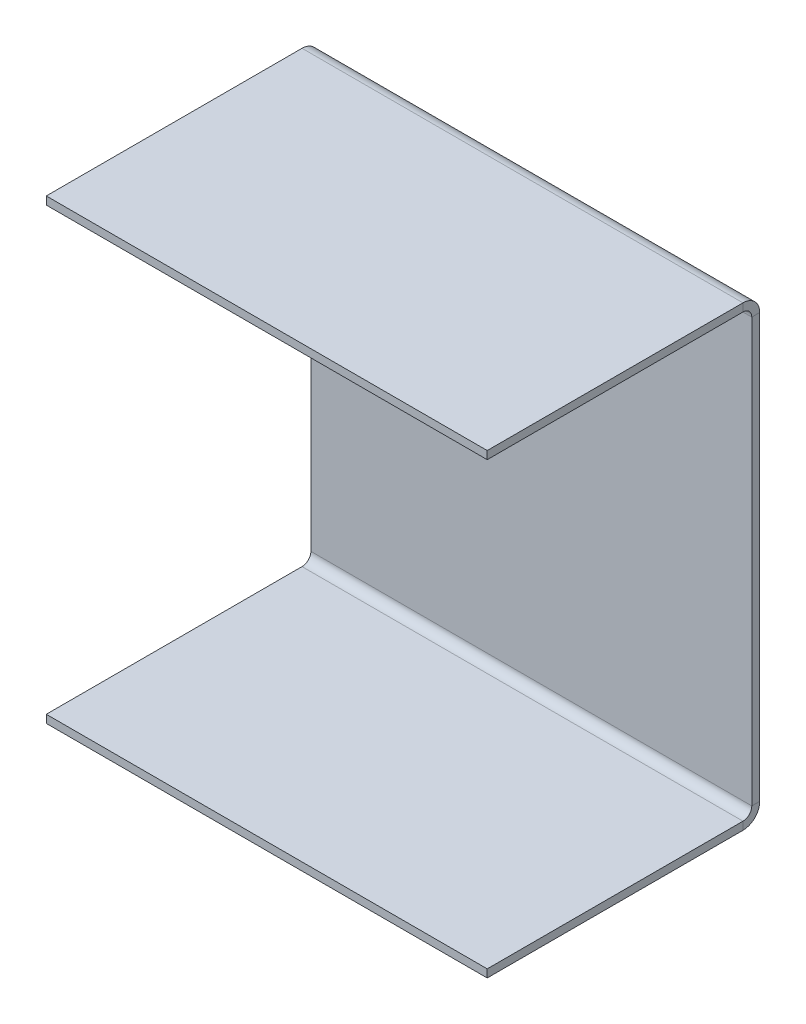
SolidWorks part; units mm, degrees
note: The reader was unsure of these and kept them because the rebuilt part matched: flange length of "Edge-Flange1", "Edge-Flange2".
ref_plane "Front Plane" through (0, 0, 0) normal (0, 0, 1) x (1, 0, 0)
ref_plane "Top Plane" through (0, 0, 0) normal (0, 1, 0) x (1, 0, 0)
ref_plane "Right Plane" through (0, 0, 0) normal (1, 0, 0) x (0, 0, -1)
sketch "Sketch1" plane through (0, 0, 0) normal (0, 0, 1) x (1, 0, 0)
  line L0 (25, 25) -> (-25, -25) construction
  line L1 (-25, 25) -> (25, 25)
  line L2 (-25, 25) -> (-25, -25)
  line L3 (-25, -25) -> (25, -25)
  line L4 (25, 25) -> (25, -25)
  point P4 (0, 0)
  dimension "D1" = 50
  dimension "D2" = 50
base flange "Base-Flange1" sketch "Sketch1" thickness 0.9 reverse thickness direction no parameters "D1"=1
edge flange "Edge-Flange1" sketch "Sketch10" flange angle 90 flange length 30 flange position material outside bend radius 1 thickness 0.9 relief rectangular parameters "D6"=10
sketch "Sketch10" plane through (0, 25, 0) normal (0, 1, 0) x (-1, 0, 0)
  line L0 (-25, 0) -> (25, 0) construction
  line L1 (-25, 0) -> (25, 0)
  line L2 (-25, 0) -> (-25, 30)
  line L3 (-25, 30) -> (25, 30)
  line L4 (25, 30) -> (25, 0)
bend "EdgeBend1" bend radius 1 bend angle 90 parameters "D5"=1
edge flange "Edge-Flange2" sketch "Sketch13" flange angle 90 flange length 30 flange position material outside bend radius 1 thickness 0.9 relief rectangular parameters "D6"=10
sketch "Sketch13" plane through (0, -25, 0) normal (0, -1, 0) x (1, 0, 0)
  line L0 (-25, 0) -> (25, 0) construction
  line L1 (-25, 0) -> (25, 0)
  line L2 (-25, 0) -> (-25, 30)
  line L3 (-25, 30) -> (25, 30)
  line L4 (25, 30) -> (25, 0)
bend "EdgeBend2" bend radius 1 bend angle 90 parameters "D5"=2
sketch "Bend-Lines1" plane through (0, 0, 0) normal (0, 1, 0) x (1, 0, 0)
sketch "Bounding-Box1" plane through (0, 0, 0) normal (0, 1, 0) x (1, 0, 0)
sheet metal parameters "Sheet-Metal1" thickness 0.9 parameters "D1"=3
flat pattern "Flat-Pattern1" [suppressed]
sketch "Bend-Lines2" plane through (0, 0, 0) normal (0, 1, 0) x (1, 0, 0)
sketch "Bounding-Box2" [suppressed] plane through (0, 0, 0) normal (0, 1, 0) x (1, 0, 0)
sheet metal parameters "Sheet-Metal2" thickness 0.9 parameters "D1"=3
flat pattern "Flat-Pattern1" [suppressed]
sketch "Bend-Lines2" plane through (0, 0, 0) normal (0, 1, 0) x (1, 0, 0)
sketch "Bounding-Box2" [suppressed] plane through (0, 0, 0) normal (0, 1, 0) x (1, 0, 0)
bend of the flat pattern "Flatten-<EdgeBend1>1"
sheet metal parameters "Sheet-Metal3" thickness 0.9 parameters "D1"=3
flat pattern "Flat-Pattern1" [suppressed]
sketch "Bend-Lines2" plane through (0, 0, 0) normal (0, 1, 0) x (1, 0, 0)
sketch "Bounding-Box2" [suppressed] plane through (0, 0, 0) normal (0, 1, 0) x (1, 0, 0)
bend of the flat pattern "Flatten-<EdgeBend1>1"
bend of the flat pattern "Flatten-<EdgeBend2>1"
